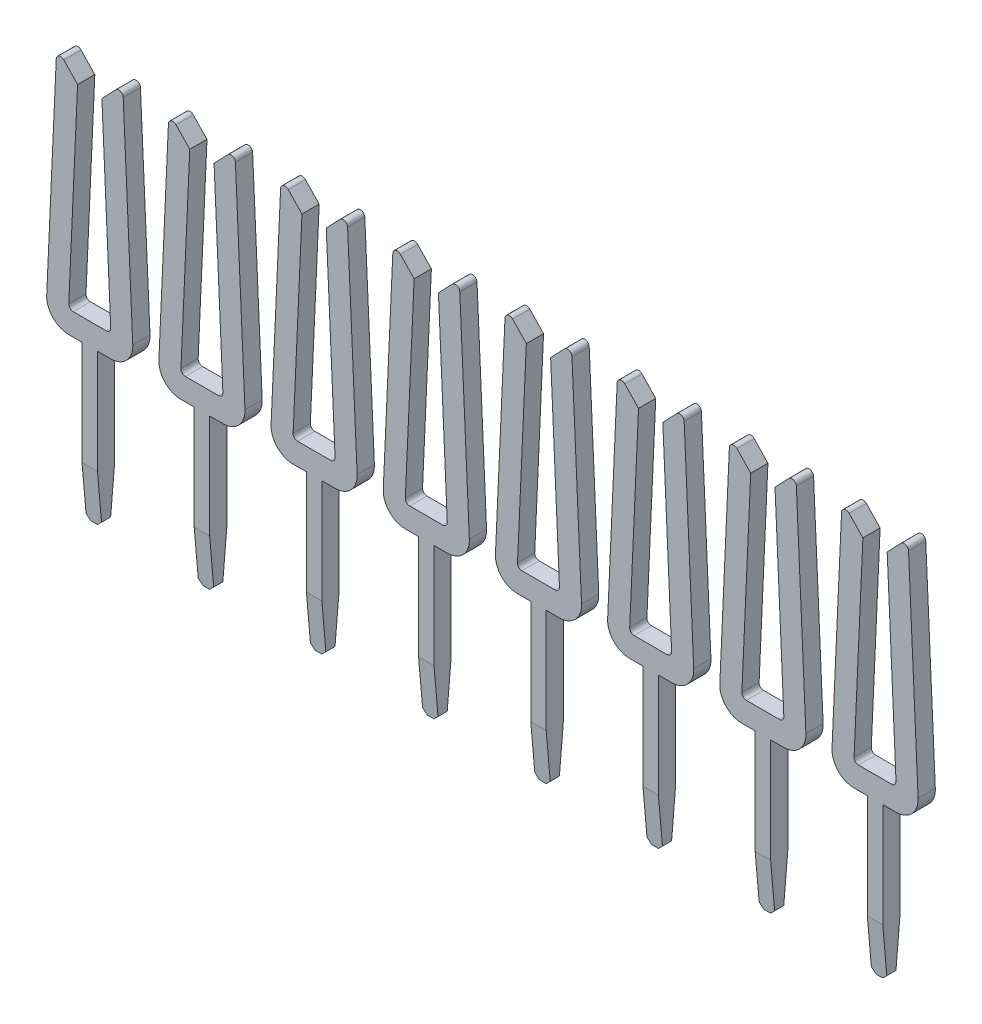
SolidWorks part; units mm, degrees
other "Шпилька"
ref_plane "Front Plane" through (0, 0, 0) normal (0, 0, 1) x (1, 0, 0)
ref_plane "Top Plane" through (0, 0, 0) normal (0, 1, 0) x (1, 0, 0)
ref_plane "Right Plane" through (0, 0, 0) normal (1, 0, 0) x (0, 0, -1)
sketch "Эскиз-Шпилька" plane through (0, 0, 0) normal (0, 0, 1) x (1, 0, 0)
  line L0 (-0.2751, 4.5045) -> (-0.586, 4.8299)
  line L1 (-0.7582, 4.7653) -> (-0.9745, 0.0228)
  line L2 (-0.475, -0.5) -> (-0.175, -0.5)
  line L3 (-0.175, -0.5) -> (-0.175, -3.9)
  line L4 (-0.175, -3.9) -> (-0.075, -4)
  line L5 (0, 4.5045) -> (0, -4) construction
  line L6 (-0.375, 0) -> (0.375, 0)
  line L7 (-0.4749, 0.1045) -> (-0.2751, 4.5045)
  line L8 (0.4749, 0.1045) -> (0.2751, 4.5045)
  line L9 (0.175, -3.9) -> (0.075, -4)
  line L10 (0.175, -0.5) -> (0.175, -3.9)
  line L11 (0.475, -0.5) -> (0.175, -0.5)
  line L12 (0.7582, 4.7653) -> (0.9745, 0.0228)
  line L13 (0.2751, 4.5045) -> (0.586, 4.8299)
  line L14 (-0.075, -4) -> (0.075, -4)
  arc A0 (-0.9745, 0.0228) -> (-0.475, -0.5) centre (-0.475, 0) ccw
  arc A1 (-0.4749, 0.1045) -> (-0.375, 0) centre (-0.375, 0.1) ccw
  arc A2 (-0.586, 4.8299) -> (-0.7582, 4.7653) centre (-0.6583, 4.7608) ccw
  arc A3 (0.586, 4.8299) -> (0.7582, 4.7653) centre (0.6583, 4.7608) cw
  arc A4 (0.4749, 0.1045) -> (0.375, 0) centre (0.375, 0.1) cw
  arc A5 (0.9745, 0.0228) -> (0.475, -0.5) centre (0.475, 0) cw
  point P26 (0, 0)
  dimension "D1" = 2.6
  dimension "D2" = 0.1
  dimension "D6" = 0.1
  dimension "D8" = 0.5
  dimension "D3" = 0.45
  dimension "D4" = 133.7
  dimension "D5" = 4.4
  dimension "D7" = 0.375
  dimension "D9" = 0.3
  dimension "D10" = 3.5
  dimension "D11" = 0.1
  dimension "D12" = 0.1
  dimension "D13" = 0.35
  dimension "D14" = 0.5
extrude "Бобышка-Шпилька" add sketch "Эскиз-Шпилька" along normal blind 0.195 and the other way blind 0.195
chamfer "Фаска1" distance 0.1 angle 85 1 edges at (0, -4, 0.195) first distance on face at (0, -4, 0)
chamfer "Фаска2" distance 0.1 angle 85 1 edges at (0, -4, -0.195) first distance on face at (0, -4, -0.05)
pattern_linear "Линейный массив1" count 8 spacing 2.54 along (-1, 0, 0) of "Бобышка-Шпилька"
